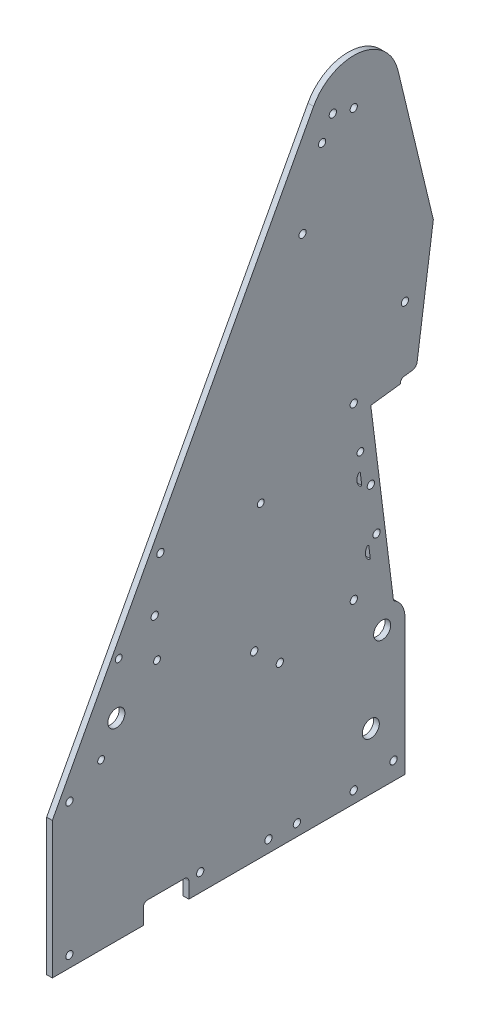
SolidWorks part; units mm, degrees
ref_plane "Front Plane" through (0, 0, 0) normal (0, 0, 1) x (1, 0, 0)
ref_plane "Top Plane" through (0, 0, 0) normal (0, 1, 0) x (1, 0, 0)
ref_plane "Right Plane" through (0, 0, 0) normal (1, 0, 0) x (0, 0, -1)
sketch "Sketch1" plane through (0, 0, 0) normal (1, 0, 0) x (0, 0, -1)
  line L0 (0, 0) -> (0, 76.2)
  line L6 (-19.05, 188.0016) -> (-2.512, 190.0852)
  line L7 (6.4943, 193.62) -> (15.875, 260.35)
  line L8 (15.875, 260.35) -> (-3.8791, 342.4892)
  line L9 (-50.965, 348.5436) -> (-196.85, 76.2)
  line L10 (-196.85, 0) -> (0, 0)
  line L11 (-196.85, 76.2) -> (-196.85, 0)
  line L12 (-19.05, 188.0016) -> (-6.35, 87.1985)
  line L13 (-0.4471, 192.7455) -> (6.4943, 193.62)
  line L14 (-2.512, 190.0852) -> (-3.1086, 194.8203) construction
  line L15 (-2.512, 190.0852) -> (6.1508, 191.1766) construction
  line L16 (6.1508, 191.1766) -> (6.4943, 193.62) construction
  arc A0 (-3.8791, 342.4892) -> (-50.965, 348.5436) centre (-28.575, 336.55) ccw
  arc A3 (0, 76.2) -> (-6.35, 87.1985) centre (-12.7, 76.2) ccw
  arc A4 (-2.512, 190.0852) -> (-0.4471, 192.7455) centre (-0.1494, 190.3829) cw
  dimension "D2" = 25.4
  dimension "D6" = 196.85
  dimension "D7" = 76.2
  dimension "D12" = 12.7
  dimension "D8" = 19.05
  dimension "D10" = 2.3813
  dimension "D1" = 28.575
  dimension "D3" = 336.55
  dimension "D4" = 25.4
  dimension "D5" = 101.6
  dimension "D9" = 6.35
  dimension ".5" = 12.7
  dimension "D11" = 76.2
  dimension "D13" = 76.2
  dimension "D14" = 15.875
  dimension "D15" = 6.35
extrude "Boss-Extrude1" add sketch "Sketch1" along normal blind 3.175
sketch "Sketch2" plane through (3.175, 0, 0) normal (1, 0, 0) x (0, 0, -1)
  line L16 (-146.05, 8.7909) -> (-146.05, -0.3034) construction
  line L17 (-123.0376, 11.1785) -> (-143.6624, 11.1785) construction
  line L18 (-120.65, -0.3034) -> (-120.65, 8.7909) construction
  line L19 (-146.05, 8.7909) -> (-146.05, 0)
  line L20 (-123.0376, 11.1785) -> (-143.6624, 11.1785)
  line L21 (-120.65, 0) -> (-120.65, 8.7909)
  line L25 (-146.05, 0) -> (-120.65, 0)
  line L26 (-196.85, 0) -> (0, 0) construction
  line L33 (-223.2996, 0) -> (-223.2996, 6.35) construction
  line L34 (-229.6496, 0) -> (-223.2996, 0) construction
  line L35 (-229.6496, 6.35) -> (-229.6496, 0) construction
  line L36 (-223.2996, 6.35) -> (-229.6496, 6.35) construction
  line L37 (-223.2996, 0) -> (-223.2996, 6.35)
  line L38 (-229.6496, 0) -> (-223.2996, 0)
  line L39 (-229.6496, 6.35) -> (-229.6496, 0)
  line L40 (-223.2996, 6.35) -> (-229.6496, 6.35)
  arc A0 (-143.6624, 11.1785) -> (-146.05, 8.7909) centre (-143.6624, 8.7909) ccw construction
  arc A1 (-120.65, 8.7909) -> (-123.0376, 11.1785) centre (-123.0376, 8.7909) ccw construction
  arc A2 (-143.6624, 11.1785) -> (-146.05, 8.7909) centre (-143.6624, 8.7909) ccw
  arc A3 (-120.65, 8.7909) -> (-123.0376, 11.1785) centre (-123.0376, 8.7909) ccw
extrude "Cut-Extrude1" cut sketch "Sketch2" against normal through all
sketch "Sketch3" plane through (3.175, 0, 0) normal (1, 0, 0) x (0, 0, -1)
  point P4 (-12.7, 76.2)
hole_wizard "3/8 Clearance Hole1" positions "Sketch3" profile "Sketch4" hole size "3/8" standard "ANSI Inch" end condition up to next
sketch "Sketch4" plane through (3.175, 76.2, 12.7) normal (0, 1, 0) x (0, 0, -1)
  line L0 (0, 0) -> (0, 3.175)
  line L1 (0, 3.175) -> (4.7625, 3.175)
  line L2 (4.7625, 3.175) -> (4.7625, 0)
  line L5 (4.7625, 0) -> (0, 0)
  line L11 (0, -6.35) -> (0, 107.95) construction
  dimension "Thru Hole Dia." = 9.525
  dimension "Thru Hole Depth" = 3.175
sketch "Sketch5" plane through (3.175, 0, 0) normal (1, 0, 0) x (0, 0, -1)
  line L0 (-12.7, 76.2) -> (19.6681, 37.0472)
  line L1 (19.6681, 37.0472) -> (18.4836, 24.56)
  line L2 (15.6221, 41.9413) -> (-25.2806, 17.5464)
  line L3 (-15.875, 19.05) -> (-25.2806, 17.5464)
  line L4 (0, 0) -> (0, 76.2) construction
  line L5 (-15.875, 19.05) -> (-27.0501, 3.6221)
  line L6 (-27.0501, 3.6221) -> (-54.7505, 169.5016)
  line L7 (50.8, 0) -> (50.8, 73.5762) construction
  dimension "D1" = 44.45
  dimension "D2" = 50.8
  dimension "D3" = 45
  dimension "D4" = 60.325
  dimension "D5" = 19.05
  dimension "D6" = 15.875
  dimension "D7" = 9.525
  dimension "D8" = 47.625
  dimension "D9" = 19.05
  dimension "D10" = 45
  dimension "D11" = 50.8
sketch "Sketch6" plane through (3.175, 0, 0) normal (1, 0, 0) x (0, 0, -1)
  circle A3 centre (-161.1018, 107.8367) radius 4.7625
  circle A5 centre (-161.1018, 107.8367) radius 6.985 construction
  circle A8 centre (-159.7995, 135.9536) radius 1.905 construction
  circle A9 centre (-138.417, 124.4998) radius 1.905 construction
  arc A10 (-167.9472, 91.0243) -> (-168.7477, 93.563) centre (-169.6472, 91.8837) ccw construction
  arc A11 (-168.7477, 93.563) -> (-171.3047, 92.8228) centre (-169.6472, 91.8837) ccw construction
  arc A12 (-171.3047, 92.8228) -> (-167.9472, 91.0243) centre (-169.6472, 91.8837) ccw construction
  circle A17 centre (-159.7995, 135.9536) radius 1.905
  circle A18 centre (-138.417, 124.4998) radius 1.905
  arc A19 (-167.9472, 91.0243) -> (-168.7477, 93.563) centre (-169.6472, 91.8837) ccw
  arc A20 (-168.7477, 93.563) -> (-171.3047, 92.8228) centre (-169.6472, 91.8837) ccw
  arc A21 (-171.3047, 92.8228) -> (-167.9472, 91.0243) centre (-169.6472, 91.8837) ccw
  dimension "D1" = 9.525
extrude "Cut-Extrude2" cut sketch "Sketch6" against normal through all
sketch "Sketch10" plane through (3.175, 0, 0) normal (1, 0, 0) x (0, 0, -1)
  circle A0 centre (-71.2566, 151.9429) radius 2.032
  dimension "D1" = 4.064
sketch "Sketch11" plane through (3.175, 0, 0) normal (1, 0, 0) x (0, 0, -1)
  circle A0 centre (-187.325, 80.5336) radius 2.032
  circle A1 centre (-187.325, 6.35) radius 2.032
  circle A2 centre (-187.325, 6.35) radius 2.032 construction
  circle A3 centre (-187.325, 80.5336) radius 2.032 construction
  dimension "D1" = 4.064
extrude "Cut-Extrude5" cut sketch "Sketch11" against normal through all
sketch "Sketch13" plane through (0, 0, 0) normal (-1, 0, 0) x (0, 0, 1)
  circle A0 centre (40.2353, 339.6611) radius 2.032
  circle A1 centre (46.232, 328.466) radius 2.032
  circle A2 centre (40.2353, 339.6611) radius 1.905 construction
  circle A3 centre (46.232, 328.466) radius 1.905 construction
  dimension "D1" = 4.064
extrude "Cut-Extrude6" cut sketch "Sketch13" against normal through all
sketch "Sketch14" plane through (3.175, 0, 0) normal (1, 0, 0) x (0, 0, -1)
  line L0 (-50.965, 348.5436) -> (-196.85, 76.2) construction
  line L1 (-136.525, 175.369) -> (-142.1225, 178.3674) construction
  circle A0 centre (-136.525, 175.369) radius 2.032
  dimension "D1" = 4.064
  dimension "D2" = 6.35
  dimension "D3" = 136.525
extrude "Cut-Extrude7" cut sketch "Sketch14" against normal through all
sketch "Sketch15" plane through (3.175, 0, 0) normal (1, 0, 0) x (0, 0, -1)
  circle A0 centre (-19.05, 31.75) radius 4.7625
  circle A1 centre (-12.7, 76.2) radius 4.7625 construction
  circle A2 centre (-28.575, 193.675) radius 2.032
  dimension "D1" = 44.45
  dimension "D3" = 4.064
  dimension "D2" = 6.35
  dimension "D4" = 161.925
  dimension "D5" = 9.525
extrude "Cut-Extrude8" cut sketch "Sketch15" against normal through all
sketch "Sketch16" plane through (3.175, 0, 0) normal (1, 0, 0) x (0, 0, -1)
  line L0 (-24.978, 158.8539) -> (-24.0851, 151.7662)
  line L1 (-6.35, 87.1985) -> (-19.05, 188.0016) construction
  line L2 (-20.2155, 121.0527) -> (-21.0031, 120.9535)
  line L3 (-24.978, 158.8539) -> (-25.7656, 158.7547)
  line L4 (-24.0851, 151.7662) -> (-24.8726, 151.667)
  line L5 (-12.7, 137.6001) -> (-26.6484, 135.8427) construction
  line L6 (-19.3226, 113.965) -> (-20.1101, 113.8658)
  line L7 (-19.3226, 113.965) -> (-20.2155, 121.0527)
  line L8 (-25.3253, 161.6102) -> (-23.7378, 149.0099) construction
  arc A0 (-25.7656, 158.7547) -> (-24.8726, 151.667) centre (-21.7352, 155.6624) ccw
  arc A1 (-20.1101, 113.8658) -> (-21.0031, 120.9535) centre (-16.9727, 117.8612) cw
  circle A2 centre (-19.0126, 149.6052) radius 2.032
  circle A3 centre (-15.8376, 124.4044) radius 2.032
  point P2 (-24.5315, 155.31)
  dimension "D2" = 0.7937
  dimension "D3" = 5.08
  dimension "D5" = 4.064
  dimension "D1" = 7.1437
  dimension "D4" = 38.1
  dimension "D6" = 4.7625
  dimension "D7" = 25.4
extrude "Cut-Extrude9" cut sketch "Sketch16" against normal up to next
fillet "Fillet1" radius 3.175 1 edges at (1.5875, 193.62, -6.4943)
sketch "Sketch17" plane through (3.175, 0, 0) normal (1, 0, 0) x (0, 0, -1)
  circle A0 centre (-6.35, 9.9085) radius 2.032
  circle A1 centre (-76.2, 6.7335) radius 2.032
  circle A2 centre (-114.3, 9.9085) radius 2.032
  circle A3 centre (-114.3, 9.9085) radius 1.905 construction
  circle A5 centre (-6.35, 9.9085) radius 1.905 construction
  dimension "D1" = 4.064
  dimension "D2" = 38.1
  dimension "D3" = 3.175
extrude "Cut-Extrude10" cut sketch "Sketch17" against normal through all
sketch "Sketch18" plane through (0, 0, 0) normal (-1, 0, 0) x (0, 0, 1)
  line L0 (50.965, 348.5436) -> (196.85, 76.2) construction
  circle A0 centre (0, 228.6) radius 2.032
  circle A1 centre (69.85, 88.9) radius 2.032
  circle A2 centre (139.7, 146.5801) radius 2.032
  circle A3 centre (57.15, 289.9291) radius 2.032
  dimension "D1" = 4.064
  dimension "D2" = 228.6
  dimension "D4" = 17.145
  dimension "D5" = 139.7
  dimension "D6" = 22.225
  dimension "D7" = 57.15
  dimension "D8" = 69.85
  dimension "D9" = 88.9
extrude "Cut-Extrude11" cut sketch "Sketch18" against normal through all
sketch "Sketch19" plane through (0, 0, 0) normal (-1, 0, 0) x (0, 0, 1)
  circle A0 centre (28.575, 336.55) radius 2.032
  arc A1 (50.965, 348.5436) -> (3.8791, 342.4892) centre (28.575, 336.55) ccw construction
  dimension "D1" = 4.064
extrude "Cut-Extrude12" cut sketch "Sketch19" against normal through all
sketch "Sketch20" plane through (3.175, 0, 0) normal (1, 0, 0) x (0, 0, -1)
  line L0 (-84.1375, 101.6) -> (-28.5243, 98.6854) construction
  line L1 (-84.1375, 101.6) -> (-84.1375, 99.4903) construction
  circle A0 centre (-28.5243, 98.6854) radius 2.032
  circle A1 centre (-84.1375, 101.6) radius 2.032
  dimension "D2" = 4.064
  dimension "D1" = 55.6895
  dimension "D3" = 87
  dimension "D4" = 84.1375
  dimension "D5" = 101.6
extrude "Cut-Extrude13" cut sketch "Sketch20" against normal through all
sketch "Sketch22" plane through (3.175, 0, 0) normal (1, 0, 0) x (0, 0, -1)
  circle A0 centre (-80.4818, 171.3543) radius 1.905
  circle A1 centre (-24.8687, 168.4397) radius 1.905
  dimension "D1" = 3.81
extrude "Cut-Extrude14" cut sketch "Sketch22" against normal blind 6.35
sketch "Sketch23" [suppressed] plane through (0, 0, 0) normal (-1, 0, 0) x (0, 0, 1)
  line L0 (47.625, 71.755) -> (63.5, 50.8) construction
  line L1 (63.5, 50.8) -> (68.6868, 50.8) construction
  circle A0 centre (63.5, 50.8) radius 2.032
  circle A1 centre (47.625, 71.755) radius 2.032
  dimension "D1" = 20.955
  dimension "D3" = 4.064
  dimension "D2" = 15.875
  dimension "D4" = 63.5
  dimension "D5" = 50.8
extrude "Cut-Extrude15" [suppressed] cut sketch "Sketch23" against normal through all
sketch "Sketch24" plane through (3.175, 0, 0) normal (1, 0, 0) x (0, 0, -1)
  circle A0 centre (-60.325, 6.604) radius 2.032
  circle A1 centre (-28.575, 6.604) radius 2.032
  circle A2 centre (-60.325, 6.604) radius 1.905 construction
  circle A4 centre (-28.575, 6.604) radius 1.905 construction
  dimension "D1" = 4.064
extrude "Cut-Extrude16" cut sketch "Sketch24" against normal through all
sketch "Sketch25" [suppressed] plane through (0, 0, 0) normal (-1, 0, 0) x (0, 0, 1)
  circle A0 centre (113.504, 34.3335) radius 2.032
  circle A1 centre (113.504, 71.4375) radius 2.032
  dimension "D1" = 4.064
extrude "Cut-Extrude17" [suppressed] cut sketch "Sketch25" against normal through all
